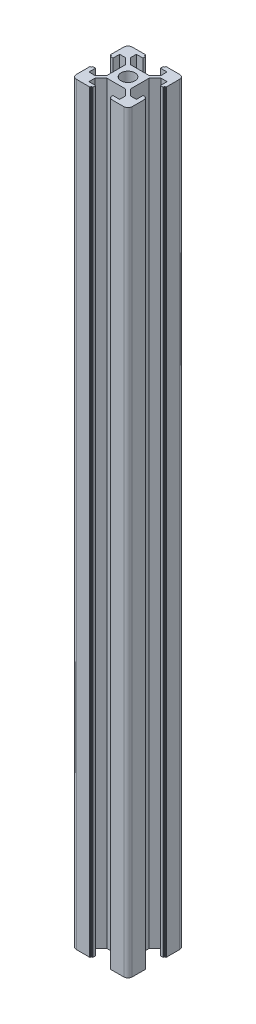
SolidWorks part; units mm, degrees
ref_plane "Front Plane" through (0, 0, 0) normal (0, 0, 1) x (1, 0, 0)
ref_plane "Top Plane" through (0, 0, 0) normal (0, 1, 0) x (1, 0, 0)
ref_plane "Right Plane" through (0, 0, 0) normal (1, 0, 0) x (0, 0, -1)
sketch "Sketch1" plane through (0, 0, 0) normal (0, 1, 0) x (1, 0, 0)
  line L0 (-8.5, 8.5) -> (8.5, 8.5)
  line L1 (-8.5, -10) -> (8.5, -10)
  line L2 (-10, -8.5) -> (-10, 8.5)
  line L3 (-8.5, 10) -> (8.5, 10)
  line L4 (10, -8.5) -> (10, 8.5)
  line L5 (-10, -10) -> (10, 10) construction
  line L6 (-10, 10) -> (10, -10) construction
  line L7 (8.5, -8.5) -> (8.5, 8.5)
  line L8 (-8.5, -8.5) -> (8.5, -8.5)
  line L9 (-8.5, -8.5) -> (-8.5, 8.5)
  line L10 (-10.4243, 9.5757) -> (9.5757, -10.4243)
  line L11 (-9.5757, -10.4243) -> (10.4243, 9.5757)
  line L12 (-9.5757, 10.4243) -> (10.4243, -9.5757)
  line L13 (-10.4243, -9.5757) -> (9.5757, 10.4243)
  line L14 (-9.5, -8.5) -> (-9.5, 8.5)
  line L15 (-10, -5.5) -> (10, -5.5)
  line L16 (-10, -5.5) -> (-10, 5.5)
  line L17 (-10, 5.5) -> (10, 5.5)
  line L18 (10, -5.5) -> (10, 5.5)
  line L19 (-10, -5.5) -> (10, 5.5) construction
  line L20 (-10, 5.5) -> (10, -5.5) construction
  line L21 (5.5, -10) -> (-5.5, -10)
  line L22 (5.5, -10) -> (5.5, 10)
  line L23 (5.5, 10) -> (-5.5, 10)
  line L24 (-5.5, -10) -> (-5.5, 10)
  line L25 (5.5, -10) -> (-5.5, 10) construction
  line L26 (5.5, 10) -> (-5.5, -10) construction
  line L27 (10, -3.1) -> (-10, -3.1)
  line L28 (10, -3.1) -> (10, 3.1)
  line L29 (10, 3.1) -> (-10, 3.1)
  line L30 (-10, -3.1) -> (-10, 3.1)
  line L31 (10, -3.1) -> (-10, 3.1) construction
  line L32 (10, 3.1) -> (-10, -3.1) construction
  line L33 (10, -3.6) -> (-10, -3.6)
  line L34 (10, -3.6) -> (10, 3.6)
  line L35 (10, 3.6) -> (-10, 3.6)
  line L36 (-10, -3.6) -> (-10, 3.6)
  line L37 (10, -3.6) -> (-10, 3.6) construction
  line L38 (10, 3.6) -> (-10, -3.6) construction
  line L39 (-8.5, 9.5) -> (8.5, 9.5)
  line L40 (9.5, -8.5) -> (9.5, 8.5)
  line L41 (-8.5, -9.5) -> (8.5, -9.5)
  arc A0 (-8.5, 10) -> (-10, 8.5) centre (-8.5, 8.5) ccw
  arc A1 (10, 8.5) -> (8.5, 10) centre (8.5, 8.5) ccw
  arc A2 (8.5, -10) -> (10, -8.5) centre (8.5, -8.5) ccw
  arc A3 (-10, -8.5) -> (-8.5, -10) centre (-8.5, -8.5) ccw
  arc A4 (8.5, 8.5) -> (8.5, 8.5) centre (8.5, 8.5) ccw
  arc A5 (8.5, -8.5) -> (8.5, -8.5) centre (8.5, -8.5) ccw
  arc A6 (-8.5, -8.5) -> (-8.5, -8.5) centre (-8.5, -8.5) ccw
  arc A7 (-8.5, 8.5) -> (-8.5, 8.5) centre (-8.5, 8.5) ccw
  circle A8 centre (0, 0) radius 2.5
  arc A9 (-8.5, 9.5) -> (-9.5, 8.5) centre (-8.5, 8.5) ccw
  arc A10 (9.5, 8.5) -> (8.5, 9.5) centre (8.5, 8.5) ccw
  arc A11 (8.5, -9.5) -> (9.5, -8.5) centre (8.5, -8.5) ccw
  arc A12 (-9.5, -8.5) -> (-8.5, -9.5) centre (-8.5, -8.5) ccw
  point P0 (0, 0)
  point P38 (0, 0)
  point P43 (0, 0)
  dimension "D3" = 1.5
  dimension "D4" = 1.5
  dimension "D5" = 1.5
  dimension "D6" = 1.5
  dimension "D12" = 5
  dimension "D1" = 20
  dimension "D2" = 20
  dimension "D10" = 11
  dimension "D11" = 11
  dimension "D13" = 6.2
  dimension "D14" = 7.2
  dimension "D7" = 1.5
  dimension "D8" = 0.6
  dimension "D9" = 0.6
  dimension "D15" = 0.5
sketch "Sketch2" plane through (0, 0, 0) normal (0, 1, 0) x (1, 0, 0)
  line L0 (-10, -8.5) -> (-10, 8.5) construction
  line L1 (-8.5, 10) -> (8.5, 10) construction
  line L2 (10, -8.5) -> (10, 8.5) construction
  line L3 (-8.5, -10) -> (8.5, -10) construction
  line L4 (-10, -8.5) -> (-10, 8.5)
  line L5 (-8.5, 10) -> (8.5, 10)
  line L6 (10, -8.5) -> (10, 8.5)
  line L7 (-8.5, -10) -> (8.5, -10)
  arc A0 (-8.5, 10) -> (-10, 8.5) centre (-8.5, 8.5) ccw construction
  arc A1 (10, 8.5) -> (8.5, 10) centre (8.5, 8.5) ccw construction
  arc A2 (8.5, -10) -> (10, -8.5) centre (8.5, -8.5) ccw construction
  arc A3 (-10, -8.5) -> (-8.5, -10) centre (-8.5, -8.5) ccw construction
  arc A4 (-8.5, 10) -> (-10, 8.5) centre (-8.5, 8.5) ccw
  arc A5 (10, 8.5) -> (8.5, 10) centre (8.5, 8.5) ccw
  arc A6 (8.5, -10) -> (10, -8.5) centre (8.5, -8.5) ccw
  arc A7 (-10, -8.5) -> (-8.5, -10) centre (-8.5, -8.5) ccw
extrude "Boss-Extrude1" add sketch "Sketch2" along normal blind 270
sketch "Sketch3" plane through (0, 270, 0) normal (0, 1, 0) x (1, 0, 0)
  line L3 (4.2, -4.2) -> (-4.2, -4.2)
  line L4 (4.2, -4.2) -> (4.2, 4.2)
  line L5 (4.2, 4.2) -> (-4.2, 4.2)
  line L6 (-4.2, -3.3515) -> (-4.2, 3.3515)
  line L7 (4.2, -4.2) -> (-4.2, 4.2) construction
  line L8 (4.2, 4.2) -> (-4.2, -4.2) construction
  line L10 (-10.4243, 9.5757) -> (9.5757, -10.4243) construction
  line L11 (-9.5757, 10.4243) -> (10.4243, -9.5757) construction
  line L12 (-10.4243, 9.5757) -> (-4.2, 3.3515)
  line L13 (-9.5757, 10.4243) -> (10.4243, -9.5757)
  line L15 (-8.5, -8.5) -> (-8.5, 8.5) construction
  line L16 (-8.5, -8.5) -> (-8.5, -3.1)
  line L17 (-10, 5.5) -> (10, 5.5) construction
  line L19 (10, -3.1) -> (-10, -3.1) construction
  line L20 (10, -3.6) -> (-10, -3.6) construction
  line L22 (10, 3.6) -> (-10, 3.6) construction
  line L23 (-10, -8.5) -> (-10, 8.5) construction
  line L24 (-10.4243, -9.5757) -> (9.5757, 10.4243) construction
  line L25 (-8.5, 5.5) -> (10, 5.5)
  line L26 (-10, -5.5) -> (10, -5.5) construction
  line L27 (10, -3.1) -> (-4.2, -3.1)
  line L28 (10, -3.6) -> (-4.4485, -3.6)
  line L29 (-10, -5.5) -> (10, -5.5)
  line L30 (10, 3.6) -> (-4.4485, 3.6)
  line L31 (-10, -8.5) -> (-10, -3.8)
  line L32 (-10.4243, -9.5757) -> (-4.2, -3.3515)
  line L33 (-10, 3.8) -> (-10, 8.5)
  line L34 (10, 3.1) -> (-10, 3.1) construction
  line L35 (10, 3.1) -> (-4.2, 3.1)
  line L36 (-9.5, -3.6) -> (-9.8, -3.6)
  line L37 (-8.5, -3.1) -> (-9.3, -3.1)
  line L38 (-9.5, 3.3) -> (-9.5, 3.6)
  line L39 (-8.5, 3.1) -> (-8.5, 8.5)
  line L40 (-9.5, 3.6) -> (-9.8, 3.6)
  line L41 (-9.5, -3.6) -> (-9.5, -3.3)
  line L42 (4.6515, -5.5) -> (10, -5.5)
  line L43 (-8.5, 3.1) -> (-9.3, 3.1)
  line L44 (-9.5, -8.5) -> (-9.5, 8.5) construction
  line L45 (-10, -8.5) -> (-10, 8.5)
  arc A0 (-9.8, -3.6) -> (-10, -3.8) centre (-9.8, -3.8) ccw
  arc A1 (-9.3, -3.1) -> (-9.5, -3.3) centre (-9.3, -3.3) ccw
  arc A2 (-9.5, 3.3) -> (-9.3, 3.1) centre (-9.3, 3.3) ccw
  arc A3 (-10, 3.8) -> (-9.8, 3.6) centre (-9.8, 3.8) ccw
  circle A6 centre (0, 0) radius 2.5 construction
  circle A7 centre (0, 0) radius 2.5
  point P0 (0, 0)
  point P55 (-9.5, 3.1)
  line M12 (-10, 8.5) -> (-10, -8.5)
  dimension "D2" = 0.2
  dimension "D3" = 0.2
  dimension "D4" = 0.2
  dimension "D5" = 0.2
  dimension "D7" = 4.3
extrude "Cut-Extrude1" cut sketch "Sketch3" against normal through all contours L39 L43 L38 L40 L36 L41 L37 L16 L29 L32 L6 L12 L25 M12 | L13 A7 | L13 A7 region at (-7.0241, 270, 0) region at (-0.5269, 270, 0.5269) region at (0.9842, 270, -0.9842)
ref_axis "Axis1" through (0, -20, 0) along (0, 1, 0)
pattern_circular "CirPattern1" count 4 over 360 about axis through (0, -20, 0) along (0, 1, 0) of "Cut-Extrude1"
sketch "Sketch4" plane through (0, 270, 0) normal (0, 1, 0) x (1, 0, 0)
sketch "Sketch5" plane through (0, 270, 0) normal (0, 1, 0) x (1, 0, 0)
  line L0 (-8.5, 3.1) -> (-9.3, 3.1) construction
  line L1 (-8.5, -3.1) -> (-9.3, -3.1) construction
  dimension "D1" = 6.2
